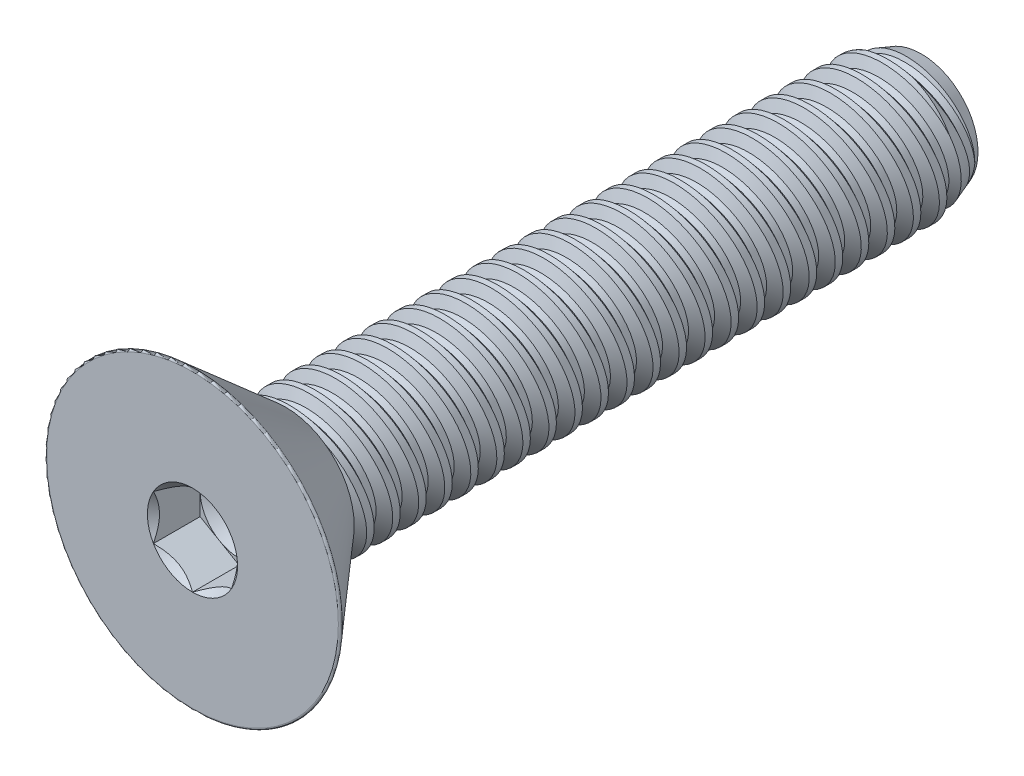
SolidWorks part; units mm, degrees
material "AISI 4340 Steel, normalized"
ref_plane "Front" through (0, 0, 0) normal (0, 0, 1) x (1, 0, 0)
ref_plane "Top" through (0, 0, 0) normal (0, 1, 0) x (1, 0, 0)
ref_plane "Right" through (0, 0, 0) normal (1, 0, 0) x (0, 0, -1)
sketch "Sketch1" plane through (0, 0, 0) normal (1, 0, 0) x (0, 0, -1)
  line L0 (0, 0) -> (-2.8448, 0) construction
  line L1 (0, 0) -> (19.3802, 0)
  line L2 (0, 0) -> (0, 2.0828)
  line L3 (0, 2.0828) -> (19.3802, 2.0828)
  line L4 (19.3802, 0) -> (19.3802, 2.0828)
  line L5 (0, -2.0828) -> (19.3802, -2.0828) construction
  dimension "D1" = 19.3802
  dimension "Thread Dia" = 4.1656
  dimension "Length" = 22.225
  dimension "Head Height" = 2.8448
revolve "Revolve1" add sketch "Sketch1" angle 360 about L0
ref_plane "Plane1" through (0, 0, 2.8448) normal (0, 0, 1) x (1, 0, 0)
sketch "Sketch2" plane through (0, 0, 0) normal (1, 0, 0) x (0, 0, -1)
  line L0 (0, 2.0828) -> (0, -2.0828) construction
  line L1 (0, -2.0828) -> (0.7938, -2.0828) construction
  line L2 (0.7938, -2.0828) -> (0, 2.0828) construction
  line L3 (0, 2.0828) -> (0.0975, 2.1014) construction
  line L4 (0.0975, 2.1014) -> (0.7797, 2.2314)
  line L5 (0.7797, 2.2314) -> (0.6165, 1.7629)
  line L6 (0.6165, 1.7629) -> (0.4215, 1.7258)
  line L7 (0.4215, 1.7258) -> (0.0975, 2.1014)
  line L8 (0.519, 1.7443) -> (0.4386, 2.1664) construction
  line L9 (0, -2.0828) -> (19.3802, -2.0828) construction
  line L10 (0, 2.0828) -> (19.3802, 2.0828) construction
  line L12 (0.4545, 2.0828) -> (1.2483, -2.0828) construction
  line L13 (0, -0.1622) -> (1.7028, 0.1622) construction
  line L15 (0, 0) -> (0, 2.0828) construction
  point P19 (0.8514, 0)
  dimension "D1" = 60
  dimension "Thread Pitch" = 0.7937
  dimension "D2" = 0.0992
  dimension "D3" = 0.1984
  dimension "D4" = 0.7937
revolve "Cut-Revolve1" cut sketch "Sketch2" angle 360 about L13
sketch "Sketch3" plane through (0, 0, 0) normal (1, 0, 0) x (0, 0, -1)
  line L0 (19.3802, 1.7258) -> (18.3993, 2.0828)
  line L1 (18.3993, 2.0828) -> (19.3802, 2.0828)
  line L2 (19.3802, 2.0828) -> (19.3802, 1.7258)
  line L3 (0, 2.0828) -> (19.3802, 2.0828) construction
  line L4 (19.3802, 0) -> (19.3802, 2.0828) construction
  line L5 (18.3993, 0) -> (0, 0) construction
  line L6 (18.3993, 2.0828) -> (18.3993, -2.0828) construction
  line L7 (0, -2.0828) -> (19.3802, -2.0828) construction
  dimension "D1" = 20
  dimension "D2" = 4.1656
revolve "Cut-Revolve2" cut sketch "Sketch3" angle 360 about L5
pattern_linear "LPattern1" count 24 spacing 0.7937 along (0, 0, 1)
pattern_linear "LPattern2" count 2 spacing 0.7937 along (0, 0, 1)
sketch "Sketch4" plane through (0, 0, 0) normal (0, 0, 1) x (1, 0, 0)
  circle A0 centre (0, 0) radius 4.5593
  dimension "Head Dia" = 9.1186
extrude "Extrude1" add sketch "Sketch4" along normal up to surface (2.8448 mm away)
sketch "Sketch9" plane through (0, 0, 0) normal (1, 0, 0) x (0, 0, -1)
  line L0 (-2.8448, 4.5593) -> (0, 2.0864)
  line L1 (0, 2.0864) -> (0, 4.5593)
  line L2 (0, 4.5593) -> (-2.8448, 4.5593)
  line L3 (0, 0) -> (-2.8448, 0) construction
  line L6 (-2.8448, -4.5593) -> (0, -2.0864) construction
  line L7 (0, -4.5593) -> (0, 4.5593) construction
  line L8 (-2.8448, 4.5593) -> (-2.8448, -4.5593) construction
  line L9 (0, 4.5593) -> (-2.8448, 4.5593) construction
  dimension "D1" = 82
revolve "Cut-Revolve3" cut sketch "Sketch9" angle 360 about L3
fillet "Fillet1" radius 0.0508
sketch "Sketch6" plane through (0, 0, 2.8448) normal (0, 0, 1) x (1, 0, 0)
  line L1 (0, -1.3748) -> (1.1906, -0.6874)
  line L2 (1.1906, -0.6874) -> (1.1906, 0.6874)
  line L3 (1.1906, 0.6874) -> (0, 1.3748)
  line L4 (0, 1.3748) -> (-1.1906, 0.6874)
  line L5 (-1.1906, 0.6874) -> (-1.1906, -0.6874)
  line L6 (-1.1906, -0.6874) -> (0, -1.3748)
  circle A0 centre (0, 0) radius 1.1906 construction
  dimension "Hex" = 2.3813
extrude "Cut-Extrude1" cut sketch "Sketch6" against normal blind 1.4224
sketch "Sketch7" plane through (0, 0, 2.8448) normal (0, 0, 1) x (1, 0, 0)
  circle A0 centre (0, 0) radius 1.3748
extrude "Cut-Extrude4" cut sketch "Sketch7" against normal blind 1.4224 draft 45
sketch "Sketch8" plane through (0, 0, 1.4224) normal (0, 0, 1) x (1, 0, 0)
  circle A0 centre (0, 0) radius 1.1906 construction
  circle A1 centre (0, 0) radius 1.1906
extrude "Cut-Extrude5" cut sketch "Sketch8" against normal blind 0.4741 draft 60
equation "\"D2@Sketch2\"=\"Thread Pitch@Sketch2\"/8"
equation "\"D3@Sketch2\"=\"Thread Pitch@Sketch2\"/4"
equation "\"D4@Sketch2\"=\"Thread Pitch@Sketch2\""
equation "\"D3@LPattern1\"=\"Thread Pitch@Sketch2\""
equation "\"D1@Cut-Extrude1\"=\"Head Height@Sketch1\"/2"
equation "\"D1@Cut-Extrude4\"=\"D1@Cut-Extrude1\""
equation "\"D1@Cut-Extrude5\"=\"D1@Cut-Extrude1\"/3"
equation "\"D1@LPattern1\"=\"D1@Sketch1\"/\"Thread Pitch@Sketch2\""
equation "\"D3@LPattern2\"=\"Thread Pitch@Sketch2\""
